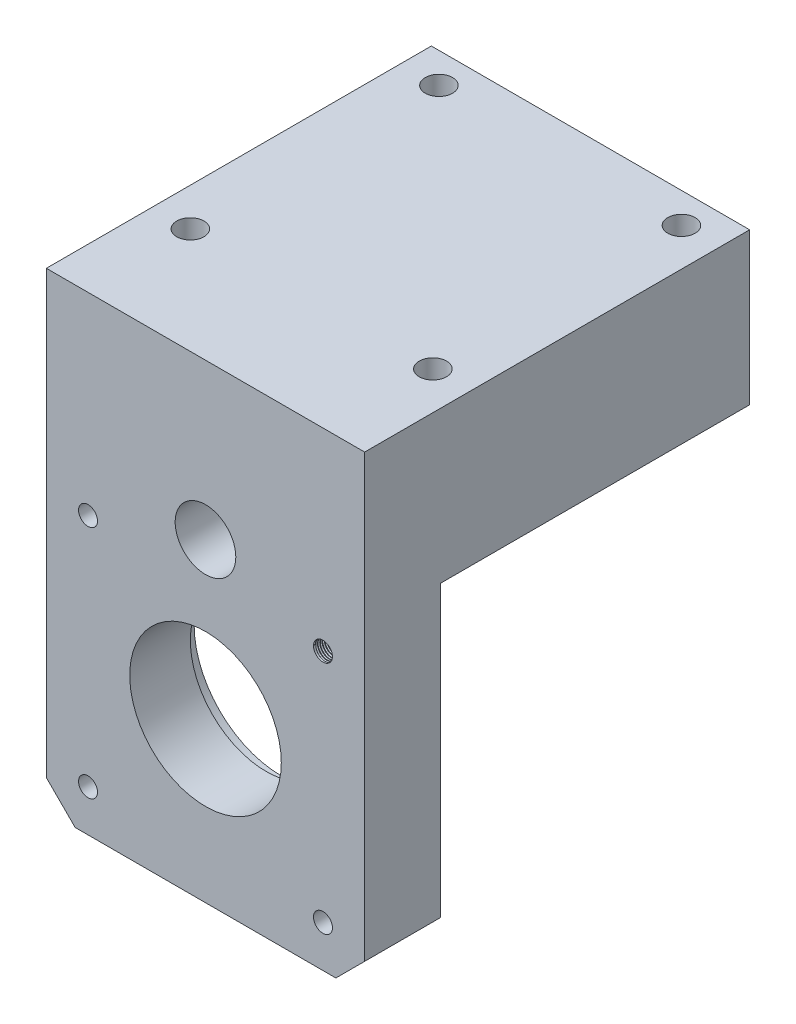
SolidWorks part; units mm, degrees
ref_plane "Front Plane" through (0, 0, 0) normal (0, 0, 1) x (1, 0, 0)
ref_plane "Top Plane" through (0, 0, 0) normal (0, 1, 0) x (1, 0, 0)
ref_plane "Right Plane" through (0, 0, 0) normal (1, 0, 0) x (0, 0, -1)
sketch "Sketch1" plane through (0, 0, 0) normal (0, 0, 1) x (1, 0, 0)
  line L1 (-17.0929, 21) -> (17.0929, 21) construction
  line L2 (21, -21) -> (-21, -21)
  line L3 (21, -21) -> (21, 21)
  line L4 (21, 21) -> (-21, 21)
  line L5 (-21, -21) -> (-21, 21)
  line L6 (21, -21) -> (-21, 21) construction
  line L7 (21, 21) -> (-21, -21) construction
  line L8 (-21, -17.0929) -> (-21, 17.0929) construction
  circle A0 centre (15.5, 15.5) radius 1.25 construction
  circle A1 centre (-15.5, 15.5) radius 1.25 construction
  circle A2 centre (-15.5, -15.5) radius 1.25 construction
  circle A3 centre (15.5, -15.5) radius 1.25 construction
  circle A4 centre (15.5, 15.5) radius 1.25
  circle A5 centre (-15.5, 15.5) radius 1.25
  circle A6 centre (-15.5, -15.5) radius 1.25
  circle A7 centre (15.5, -15.5) radius 1.25
  circle A8 centre (0, 0) radius 11.5 construction
  circle A9 centre (0, 0) radius 11.5
  point P2 (0, 0)
extrude "Boss-Extrude1" add sketch "Sketch1" along normal blind 2
sketch "Sketch2" plane through (0, 21, 0) normal (0, 1, 0) x (1, 0, 0)
  line L0 (-17.0929, 40.8) -> (17.0929, 40.8) construction
  line L1 (21, -2) -> (-21, -2)
  line L2 (21, -2) -> (21, 40.8)
  line L3 (21, 40.8) -> (-21, 40.8)
  line L4 (-21, -2) -> (-21, 40.8)
  line L5 (-21, -2) -> (-21, 0) construction
extrude "Boss-Extrude2" add sketch "Sketch2" along normal blind 15
sketch "Sketch4" plane through (0, 0, 2) normal (0, 0, 1) x (1, 0, 0)
  line L6 (-21, 36) -> (-21, -21)
  line L7 (-21, -21) -> (21, -21)
  line L8 (21, -21) -> (21, 36)
  line L9 (21, 36) -> (-21, 36)
  line L12 (-21, 36) -> (-21, -21)
  line L13 (-21, -21) -> (21, -21)
  line L14 (21, -21) -> (21, 36)
  line L15 (21, 36) -> (-21, 36)
  circle A0 centre (-15.5, -15.5) radius 1.25 construction
  circle A1 centre (-15.5, -15.5) radius 1.25
  circle A2 centre (15.5, -15.5) radius 1.25 construction
  circle A3 centre (15.5, 15.5) radius 1.25 construction
  circle A4 centre (-15.5, 15.5) radius 1.25 construction
  circle A5 centre (15.5, -15.5) radius 1.25
  circle A6 centre (15.5, 15.5) radius 1.25
  circle A7 centre (-15.5, 15.5) radius 1.25
  circle A8 centre (0, 0) radius 10
  dimension "D2" = 20
  dimension "D1" = 0
extrude "Boss-Extrude9" add sketch "Sketch4" along normal blind 8
sketch "Sketch6" plane through (0, 0, 10) normal (0, 0, 1) x (1, 0, 0)
  line L0 (15.5, 15.5) -> (-15.5, 15.5) construction
  line L1 (0, 0) -> (0, 20.5) construction
  circle A0 centre (0, 20.5) radius 4
  dimension "D1" = 8
  dimension "D2" = 5
extrude "Cut-Extrude3" cut sketch "Sketch6" against normal blind 12
thread "Thread1" pitch 0.3 profile "Thread Profile1" start angle 0, offset 0, length 10, pitch 0.3, diameter 2.5
ref_plane "Plane1" through (14.25, 15.5, 10) normal (0, -1, 0) x (-1, 0, 0)
sketch "Thread Profile1" plane through (14.25, 15.5, 10) normal (0, -1, 0) x (-1, 0, 0)
  line L0 (0, 0) -> (0, 0.3) construction
  line L1 (0, 0) -> (0.1624, 0.0937)
  line L2 (0.1624, 0.0937) -> (0.1624, 0.1312)
  line L3 (0.1624, 0.1312) -> (0, 0.225)
  line L4 (0.1624, 0.1125) -> (0, 0.1125) construction
  line L11 (0, 0) -> (0, 0.225)
  point P2 (0, 0)
  dimension "Pitch" = 0.3
  dimension "Profile_Angle" = 60
  dimension "Profile_Land" = 0.0375
  dimension "Profile_Height" = 0.1624
chamfer "Chamfer1" distance 3.8 angle 45 2 edges at (21, -21, 5) (-21, -21, 5)
sketch "Sketch7" plane through (0, 36, 0) normal (0, 1, 0) x (1, 0, 0)
  line L4 (21, -10) -> (21, 40.8)
  line L5 (21, 40.8) -> (-21, 40.8)
  line L6 (-21, 40.8) -> (-21, -10)
  line L7 (-21, -10) -> (21, -10)
  line L8 (21, -10) -> (21, 40.8)
  line L9 (21, 40.8) -> (-21, 40.8)
  line L10 (-21, 40.8) -> (-21, -10)
  line L11 (-21, -10) -> (21, -10)
  dimension "D1" = 0
extrude "Boss-Extrude10" add sketch "Sketch7" along normal blind 5
hole_wizard "CSK for M3 SFHCS1" positions "Sketch11" profile "Sketch12" countersink size "M3" standard "ANSI Metric" end condition up to next
sketch "Sketch11" plane through (0, 21, 0) normal (0, -1, 0) x (-1, 0, 0)
  line L0 (-21, 0) -> (-21, 40.8) construction
  line L1 (-21, 40.8) -> (21, 40.8) construction
  point P0 (-16, 36.8)
  dimension "D1" = 5
  dimension "D2" = 4
sketch "Sketch12" plane through (16, 21, -36.8) normal (1, 0, 0) x (0, 0, -1)
  line L0 (0, 0) -> (0, 20.001)
  line L1 (0, 20.001) -> (1.8, 20.001)
  line L2 (1.8, 20.001) -> (1.8, 1.56)
  line L3 (1.8, 1.56) -> (3.36, 0)
  line L5 (3.36, 0) -> (0, 0)
  line L6 (-1.8, 1.56) -> (-3.36, 0) construction
  line L11 (0, -6.35) -> (0, 107.95) construction
  dimension "Thru Hole Dia." = 3.6
  dimension "Thru Hole Depth" = 20.001
  dimension "Near C'Sink Dia." = 6.72
  dimension "Near C'Sink Angle" = 90
mirror "Mirror2" about plane through (0, 0, 0) normal (1, 0, 0) of "CSK for M3 SFHCS1"
ref_plane "Plane3" through (0, 0, -20.4) normal (0, 0, -1) x (-1, 0, 0)
mirror "Mirror4" about plane through (0, 0, -20.4) normal (0, 0, -1) of "Mirror2", "CSK for M3 SFHCS1"
